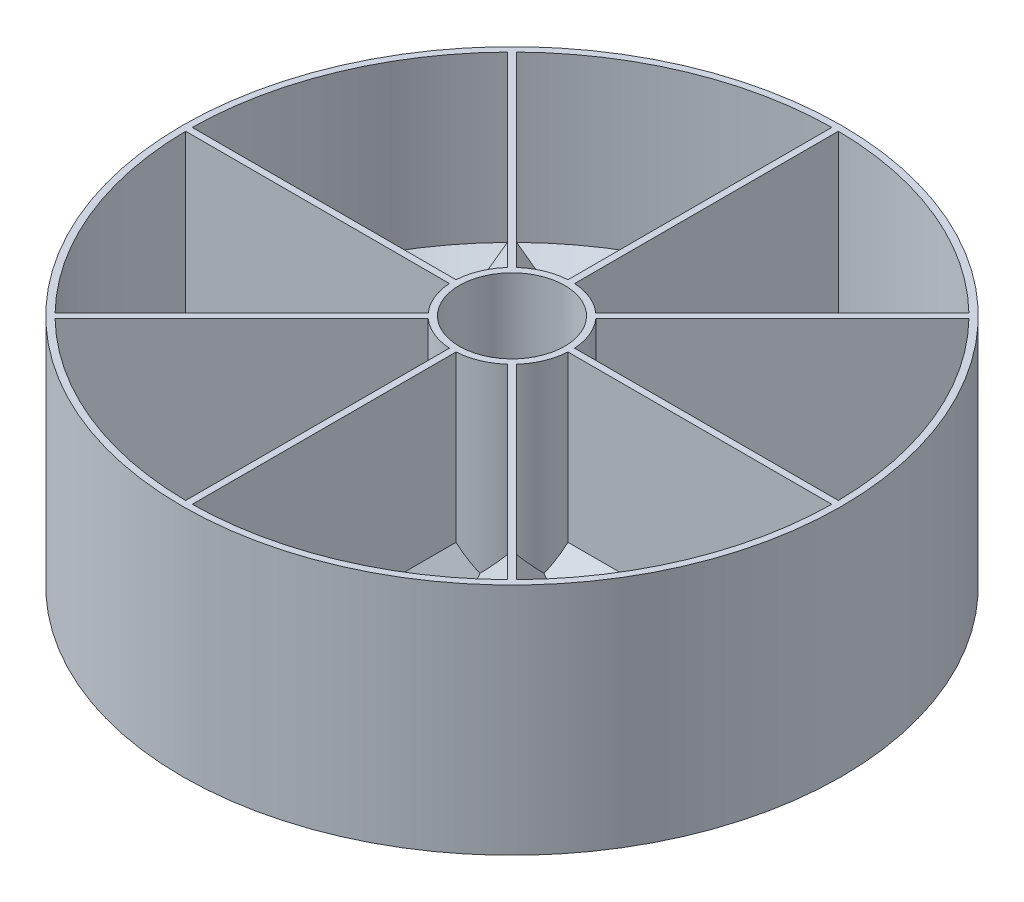
SolidWorks part; units mm, degrees
material "1.4000 (X6Cr13)"
ref_plane "Front Plane" through (0, 0, 0) normal (0, 0, 1) x (1, 0, 0)
ref_plane "Top Plane" through (0, 0, 0) normal (0, 1, 0) x (1, 0, 0)
ref_plane "Right Plane" through (0, 0, 0) normal (1, 0, 0) x (0, 0, -1)
sketch "Sketch2" plane through (0, 0, 0) normal (0, 1, 0) x (1, 0, 0)
  circle A0 centre (0, 0) radius 100
  circle A1 centre (0, 0) radius 98
  dimension "D1" = 196
extrude "Boss-Extrude2" add sketch "Sketch2" along normal blind 70
sketch "Sketch3" plane through (0, 0, 0) normal (0, 1, 0) x (1, 0, 0)
  circle A0 centre (0, 0) radius 18
  circle A1 centre (0, 0) radius 16
  dimension "D1" = 36
  dimension "D2" = 32
extrude "Boss-Extrude3" add sketch "Sketch3" along normal blind 70
sketch "Sketch4" plane through (0, 0, 0) normal (0, 1, 0) x (1, 0, 0)
  line L0 (0, -18) -> (0, -98) construction
  line L1 (-1, -17.9722) -> (-1, -97.9949)
  line L2 (1, -17.9722) -> (1, -97.9949)
  arc A2 (1, -17.9722) -> (-1, -17.9722) centre (0, 0) cw
  arc A3 (1, -97.9949) -> (-1, -97.9949) centre (0, 0) cw
  circle A4 centre (0, 0) radius 18 construction
  circle A5 centre (0, 0) radius 98 construction
  dimension "D1" = 1
  dimension "D2" = 1
extrude "Boss-Extrude4" add sketch "Sketch4" along normal blind 70 contours L0 A2 L1 | L0 A3 L2 region at (0, 0, 57.9945)
pattern_circular "CirPattern1" count 8 over 360 about axis through (0, 70, 0) along (0, -1, 0) of "Boss-Extrude4" reverse direction yes
sketch "Sketch5" plane through (0, 0, 0) normal (0, -1, 0) x (1, 0, 0)
  circle A0 centre (0, 0) radius 100
extrude "Boss-Extrude5" add sketch "Sketch5" along normal blind 1
sketch "Sketch6" plane through (0, 0, 0) normal (0, 1, 0) x (1, 0, 0)
  line L0 (-13.4154, -12.0012) -> (-70, -68.5857) construction
  line L1 (-97.9949, -1) -> (-57.9949, -1)
  line L2 (-17.9722, -1) -> (-97.9949, -1) construction
  line L3 (-70, -68.5857) -> (-41.7157, -40.3015)
  arc A0 (-97.9949, -1) -> (-70, -68.5857) centre (0, 0) ccw
  arc A1 (-57.9949, -1) -> (-41.7157, -40.3015) centre (0, 0) ccw
  dimension "D1" = 40
extrude "Cut-Extrude1" [suppressed] cut sketch "Sketch6" against normal blind 2
sketch "Sketch9" plane through (0, 0, 0) normal (0, 1, 0) x (1, 0, 0)
  circle A0 centre (0, 0) radius 16
extrude "Boss-Extrude6" add sketch "Sketch9" along normal blind 10
sketch "Sketch10" plane through (0, 10, 0) normal (0, 1, 0) x (1, 0, 0)
  line L1 (0, 16) -> (-13.8564, 8)
  line L2 (-13.8564, 8) -> (-13.8564, -8)
  line L3 (-13.8564, -8) -> (0, -16)
  line L4 (0, -16) -> (13.8564, -8)
  line L5 (13.8564, -8) -> (13.8564, 8)
  line L6 (13.8564, 8) -> (0, 16)
  circle A0 centre (0, 0) radius 16 construction
extrude "Cut-Extrude2" cut sketch "Sketch10" against normal through all
chamfer "Chamfer1" distance 20 angle 45 32 edges at (-6.8883, 0, -16.6298) (-16.6298, 0, -6.8883) (-16.6298, 0, 6.8883) (-6.8883, 0, 16.6298) (6.8883, 0, 16.6298) (16.6298, 0, 6.8883) (16.6298, 0, -6.8883) (6.8883, 0, -16.6298) (-57.9835, 0, -1) (-90.5402, 0, -37.503) (-41.7077, 0, -40.2935) (-40.2935, 0, -41.7077) (-37.503, 0, -90.5402) (-1, 0, -57.9835) (1, 0, -57.9835) (37.503, 0, -90.5402) (40.2935, 0, -41.7077) (41.7077, 0, -40.2935) (90.5402, 0, -37.503) (57.9835, 0, -1) (57.9835, 0, 1) (90.5402, 0, 37.503) (41.7077, 0, 40.2935) (40.2935, 0, 41.7077) (37.503, 0, 90.5402) (1, 0, 57.9835) (-41.7077, 0, 40.2935) (-90.5402, 0, 37.503) (-57.9835, 0, 1) (-40.2935, 0, 41.7077) (-37.503, 0, 90.5402) (-1, 0, 57.9835)
sketch "Sketch11" plane through (0, 0, 0) normal (0, 1, 0) x (1, 0, 0)
  line L0 (-21, -50.6985) -> (-38.2686, -67.967)
  line L1 (-38.2686, -67.967) -> (-21, -75.1199)
  line L2 (-21, -75.1199) -> (-21, -50.6985)
extrude "Cut-Extrude3" cut sketch "Sketch11" against normal through all
pattern_circular "CirPattern2" count 8 over 360 about axis through (0, 70, 0) along (0, -1, 0) of "Cut-Extrude3" reverse direction yes
